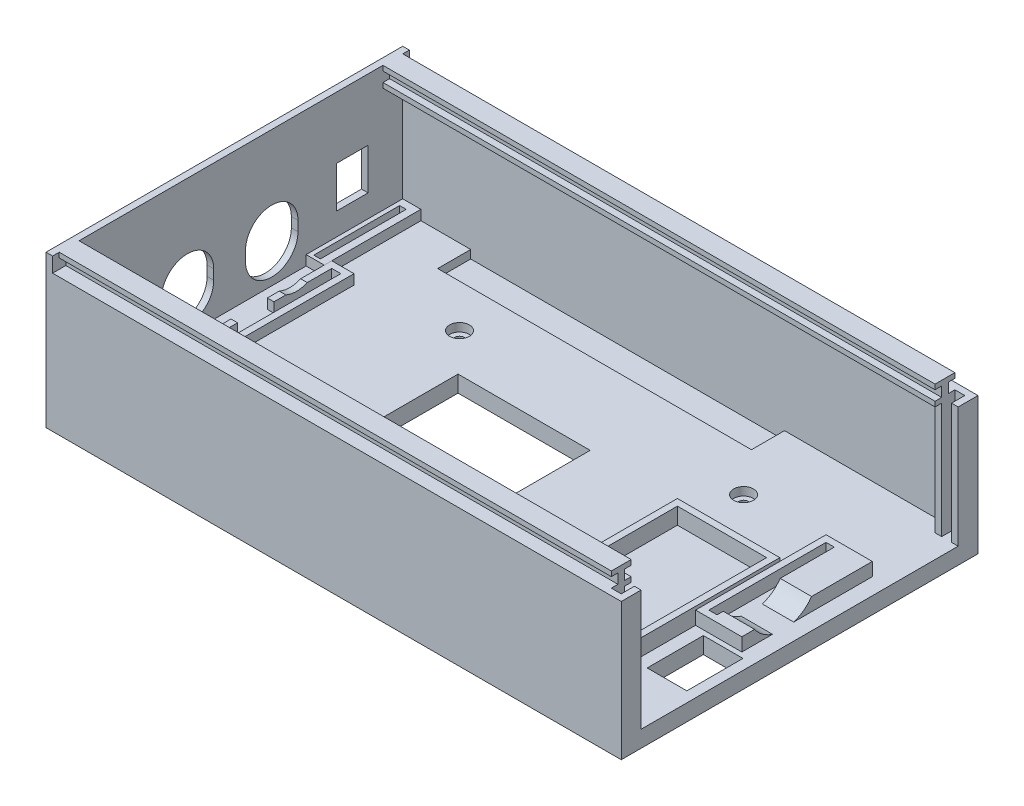
SolidWorks part; units mm, degrees
other "초음파센서_받침"
other "하단베이스"
other "모터헷_받침"
other "전자석_받침"
other "카메라_받침"
ref_plane "정면" through (0, 0, 0) normal (0, 0, 1) x (1, 0, 0)
ref_plane "윗면" through (0, 0, 0) normal (0, 1, 0) x (1, 0, 0)
ref_plane "우측면" through (0, 0, 0) normal (1, 0, 0) x (0, 0, -1)
sketch "스케치1" plane through (0, 0, 0) normal (0, 1, 0) x (1, 0, 0)
  line L1 (-87.075, 54) -> (87.075, 54)
  line L2 (-87.075, 54) -> (-87.075, -54)
  line L3 (-87.075, -54) -> (87.075, -54)
  line L4 (87.075, 54) -> (87.075, -54)
  line L5 (-87.075, 54) -> (87.075, -54) construction
  line L6 (-87.075, -54) -> (87.075, 54) construction
  point P0 (0, 0)
  dimension "D1" = 174.15
  dimension "D2" = 108
extrude "보스-돌출1" add sketch "스케치1" along normal blind 63
sketch "스케치2" plane through (87.075, 0, 0) normal (1, 0, 0) x (0, 0, -1)
  line L0 (-54, 0) -> (54, 0) construction
  line L1 (-52, 61) -> (52, 61)
  line L2 (-52, 61) -> (-52, 5)
  line L3 (-52, 5) -> (52, 5)
  line L4 (52, 61) -> (52, 5)
  line L5 (54, 63) -> (54, 0) construction
  line L6 (-54, 63) -> (-54, 0) construction
  line L7 (-54, 63) -> (54, 63) construction
  dimension "D1" = 5
  dimension "D2" = 2
  dimension "D3" = 2
  dimension "D4" = 2
extrude "컷-돌출1" cut sketch "스케치2" against normal blind 172.15
sketch "스케치3" plane through (0, 63, 0) normal (0, 1, 0) x (1, 0, 0)
  line L4 (87.075, -54) -> (87.075, 54)
  line L5 (87.075, 54) -> (-87.075, 54)
  line L6 (-87.075, 54) -> (-87.075, -54)
  line L7 (-87.075, -54) -> (87.075, -54)
  line L8 (87.075, -54) -> (87.075, 54)
  line L9 (87.075, 54) -> (-87.075, 54)
  line L10 (-87.075, 54) -> (-87.075, -54)
  line L11 (-87.075, -54) -> (87.075, -54)
  dimension "D1" = 0
extrude "컷-돌출2" cut sketch "스케치3" against normal blind 2
sketch "스케치4" plane through (0, 5, 0) normal (0, 1, 0) x (1, 0, 0)
  line L6 (-74.825, 23) -> (-74.825, -23)
  line L7 (-77.575, -23) -> (-74.825, -23)
  line L8 (-77.575, 23) -> (-77.575, -23)
  line L9 (-77.575, 23) -> (-74.825, 23)
  line L10 (-79.575, 25) -> (-72.825, 25)
  line L11 (-72.825, 25) -> (-72.825, -25)
  line L12 (-79.575, -25) -> (-72.825, -25)
  line L13 (-79.575, 25) -> (-79.575, -25)
  dimension "D6" = 2
sketch "스케치5" plane through (-87.075, 0, 0) normal (-1, 0, 0) x (0, 0, 1)
  line L0 (-12.34, 15.25) -> (-12.34, 18.25) construction
  line L1 (13.16, 15.25) -> (13.16, 18.25) construction
  line L2 (-20.28, 18.25) -> (-20.28, 15.25)
  line L3 (-4.4, 18.25) -> (-4.4, 15.25)
  line L4 (5.22, 18.25) -> (5.22, 15.25)
  line L5 (21.1, 18.25) -> (21.1, 15.25)
  arc A0 (-20.28, 15.25) -> (-4.4, 15.25) centre (-12.34, 15.25) ccw
  arc A1 (5.22, 15.25) -> (21.1, 15.25) centre (13.16, 15.25) ccw
  arc A2 (-4.4, 18.25) -> (-20.28, 18.25) centre (-12.34, 18.25) ccw
  arc A3 (21.1, 18.25) -> (5.22, 18.25) centre (13.16, 18.25) ccw
  dimension "D2" = 15.88
  dimension "D3" = 3
  dimension "D4" = 15.88
  dimension "D1" = 3
extrude "컷-돌출3" cut sketch "스케치5" against normal blind 10
extrude "보스-돌출2" add sketch "스케치4" along normal blind 3 separate body
sketch "스케치6" plane through (-79.575, 0, 0) normal (-1, 0, 0) x (0, 0, 1)
  circle A0 centre (-12.34, 15.25) radius 7.94
  circle A1 centre (13.16, 15.25) radius 7.94
extrude "컷-돌출4" cut sketch "스케치6" against normal blind 3
sketch "스케치7" plane through (-79.575, 0, 0) normal (-1, 0, 0) x (0, 0, 1)
  line L0 (-9.1025, 8) -> (9.9225, 8) construction
  line L1 (-5.5, 8) -> (5.5, 8)
  line L2 (-5.5, 8) -> (-5.5, 5)
  line L3 (-5.5, 5) -> (5.5, 5)
  line L4 (5.5, 8) -> (5.5, 5)
  line L5 (-25, 5) -> (25, 5) construction
  line L6 (-25, 8) -> (-25, 5) construction
  dimension "D1" = 11
  dimension "D2" = 19.5
extrude "컷-돌출5" cut sketch "스케치7" against normal blind 3
sketch "스케치8" plane through (87.075, 0, 0) normal (1, 0, 0) x (0, 0, -1)
  line L0 (0, 0) -> (0, 15) construction
  circle A0 centre (0, 15) radius 4
  dimension "D2" = 8
  dimension "D1" = 15
sketch "스케치13" plane through (0, 5, 0) normal (0, 1, 0) x (1, 0, 0)
  line L0 (70.075, 25) -> (70.075, -10.5)
  line L5 (70.075, -10.5) -> (72.575, -10.5)
  line L6 (72.575, 25) -> (72.575, -10.5)
  line L7 (70.075, 25) -> (72.575, 25)
  line L8 (68.075, 27) -> (68.075, -12.5)
  line L9 (68.075, -12.5) -> (74.575, -12.5)
  line L10 (74.575, 27) -> (74.575, -12.5)
  line L11 (68.075, 27) -> (74.575, 27)
  dimension "D2" = 2
extrude "보스-돌출5" add sketch "스케치13" along normal blind 4 separate body
sketch "스케치14" plane through (74.575, 0, 0) normal (1, 0, 0) x (0, 0, -1)
  line L4 (-12.5, 5) -> (27, 5)
  line L5 (27, 5) -> (27, 9)
  line L6 (27, 9) -> (-12.5, 9)
  line L7 (-12.5, 9) -> (-12.5, 5)
  line L8 (-12.5, 5) -> (27, 5)
  line L9 (27, 5) -> (27, 9)
  line L10 (27, 9) -> (-12.5, 9)
  line L11 (-12.5, 9) -> (-12.5, 5)
  dimension "D1" = 0
extrude "보스-돌출6" add sketch "스케치14" along normal up to surface (12.5 mm away) up to face at (87.075, 31.75, 0)
sketch "스케치15" plane through (87.075, 0, 0) normal (1, 0, 0) x (0, 0, -1)
  circle A0 centre (0, 15) radius 10.5
  line M1 (-12.5, 5) -> (27, 5)
  line M3 (27, 9) -> (-12.5, 9)
  dimension "D1" = 21
extrude "컷-돌출9" cut sketch "스케치15" against normal up to surface (14.5 mm away) contours A0 M3 M1 region at (87.075, 7.2591, 0) up to face at (72.575, 7, -7.25)
sketch "스케치16" plane through (0, 0, 0) normal (0, -1, 0) x (-1, 0, 0)
  line L0 (-71.925, -31) -> (-71.925, -14)
  line L5 (-71.925, -14) -> (-83.925, -14)
  line L6 (-83.925, -31) -> (-83.925, -14)
  line L7 (-71.925, -31) -> (-83.925, -31)
  circle A0 centre (44.9261, -28.968) radius 1.45
  circle A1 centre (44.9263, 29.0311) radius 1.45
  circle A2 centre (-41.0739, -28.9678) radius 1.45
  circle A3 centre (-41.0728, 29.0327) radius 1.45
  dimension "D1" = 2.9
  dimension "D2" = 2.9
  dimension "D3" = 2.9
  dimension "D4" = 2.9
extrude "컷-돌출10" cut sketch "스케치16" against normal up to surface (5 mm away) contours A0 | A1 | A3 | A2 | L7 L0 L5 L6 region at (77.925, 0, 22.5) region at (-44.9261, 0, 28.968) region at (-44.9263, 0, -29.0311) region at (41.0739, 0, 28.9678) region at (41.0728, 0, -29.0327) up to face at (1, 5, 0)
sketch "스케치17" plane through (0, 5, 0) normal (0, 1, 0) x (1, 0, 0)
  circle A0 centre (-44.9263, 29.0311) radius 3
  circle A1 centre (-44.9261, -28.968) radius 3
  circle A2 centre (41.0728, 29.0327) radius 3
  circle A3 centre (41.0739, -28.9678) radius 3
  dimension "D1" = 6
  dimension "D2" = 6
  dimension "D3" = 6
  dimension "D4" = 6
extrude "컷-돌출11" cut sketch "스케치17" against normal blind 2.5
sketch "스케치19" plane through (0, 5, 0) normal (0, 1, 0) x (1, 0, 0)
  line L0 (-85.075, -52) -> (87.075, -52) construction
  line L1 (40.075, 10) -> (65.075, 10)
  line L2 (40.075, 10) -> (40.075, -52)
  line L4 (65.075, 10) -> (65.075, -52)
  line L5 (66.075, 11) -> (66.075, -52)
  line L6 (39.075, 11) -> (66.075, 11)
  line L7 (39.075, 11) -> (39.075, -52)
  line L8 (65.075, -52) -> (66.075, -52)
  line L9 (40.075, -52) -> (39.075, -52)
  line L10 (68.075, 13) -> (68.075, -52)
  line L11 (37.075, 13) -> (68.075, 13)
  line L12 (37.075, 13) -> (37.075, -52)
  line L13 (66.075, -52) -> (68.075, -52)
  line L14 (39.075, -52) -> (37.075, -52)
  line L15 (68.075, 27) -> (68.075, -12.5) construction
  circle M9 centre (41.0739, -28.9678) radius 3
  line M14 (-85.075, -52) -> (87.075, -52)
  dimension "D3" = 31
  dimension "D4" = 27
  dimension "D5" = 25
  dimension "D6" = 2
  dimension "D1" = 1
  dimension "D2" = 2
extrude "보스-돌출7" add sketch "스케치19" along normal blind 5 separate body contours L11 L12 L7 L6 L5 L10 M14 M9 region at (37.3538, 5, 28.9678)
sketch "스케치20" plane through (37.075, 0, 0) normal (-1, 0, 0) x (0, 0, 1)
  line L0 (-13, 10) -> (52, 10) construction
  line L1 (16.1526, 10) -> (25.7505, 10)
  line L2 (16.1526, 10) -> (16.1526, 5)
  line L3 (16.1526, 5) -> (25.7505, 5)
  line L4 (25.7505, 10) -> (25.7505, 5)
  line L5 (-13, 5) -> (52, 5) construction
extrude "컷-돌출13" cut sketch "스케치20" against normal blind 5
ref_plane "평면1" through (0, 46, 0) normal (0, 1, 0) x (1, 0, 0)
sketch "스케치22" plane through (0, 46, 0) normal (0, 1, 0) x (1, 0, 0)
  line L1 (-87.075, 54) -> (87.075, 54)
  line L2 (-87.075, 54) -> (-87.075, -54)
  line L3 (-87.075, -54) -> (87.075, -54)
  line L4 (87.075, 54) -> (87.075, -54)
extrude "컷-돌출14" cut sketch "스케치22" along normal up to surface (15 mm away) up to face at (0.5, 61, 0)
sketch "스케치29" plane through (0, 0, 0) normal (0, -1, 0) x (-1, 0, 0)
  line L1 (33.7542, -22.5802) -> (-6.2458, -22.5802)
  line L2 (33.7542, -22.5802) -> (33.7542, 17.4198)
  line L3 (33.7542, 17.4198) -> (-6.2458, 17.4198)
  line L4 (-6.2458, -22.5802) -> (-6.2458, 17.4198)
  dimension "D1" = 40
  dimension "D2" = 40
extrude "컷-돌출21" cut sketch "스케치29" against normal up to surface (5 mm away) up to face at (-44.9261, 5, 31.968)
sketch "스케치30" plane through (0, 5, 0) normal (0, 1, 0) x (1, 0, 0)
  line L0 (-85.075, 52) -> (87.075, 52) construction
  line L1 (-64.5028, 52) -> (30.4972, 52)
  line L2 (-64.5028, 52) -> (-64.5028, 42)
  line L3 (-64.5028, 42) -> (30.4972, 42)
  line L4 (30.4972, 52) -> (30.4972, 42)
  line L5 (30.4972, -46) -> (30.4972, 52) construction
  dimension "D1" = 10
  dimension "D2" = 95
extrude "컷-돌출22" cut sketch "스케치30" against normal blind 2.5
sketch "스케치36" plane through (0, 46, 0) normal (0, 1, 0) x (1, 0, 0)
  line L16 (-85.075, 46) -> (87.075, 46)
  line L17 (87.075, -46) -> (-85.075, -46)
  line L18 (-85.075, 52) -> (-85.075, 46)
  line L19 (87.075, 52) -> (87.075, 46)
  line L20 (87.075, -52) -> (87.075, -46)
  line L21 (-85.075, -52) -> (-85.075, -46)
  line L24 (87.075, -52) -> (-85.075, -52)
  line L25 (-85.075, -52) -> (-85.075, 52)
  line L26 (-85.075, 52) -> (87.075, 52)
  line L27 (87.075, 52) -> (87.075, 54)
  line L28 (87.075, 54) -> (-87.075, 54)
  line L29 (-87.075, 54) -> (-87.075, -54)
  line L30 (-87.075, -54) -> (87.075, -54)
  line L31 (87.075, -54) -> (87.075, -52)
  line L32 (87.075, -52) -> (-85.075, -52)
  line L33 (-85.075, -52) -> (-85.075, 52)
  line L34 (-85.075, 52) -> (87.075, 52)
  line L35 (87.075, 52) -> (87.075, 54)
  line L36 (87.075, 54) -> (-87.075, 54)
  line L37 (-87.075, 54) -> (-87.075, -54)
  line L38 (-87.075, -54) -> (87.075, -54)
  line L39 (87.075, -54) -> (87.075, -52)
  line M9 (87.075, -52) -> (-85.075, -52)
  line M10 (-85.075, -52) -> (-85.075, 52)
  line M11 (-85.075, 52) -> (87.075, 52)
  dimension "D1" = 0
  dimension "D2" = 6
extrude "보스-돌출12" add sketch "스케치36" against normal blind 6 contours L19 L16 M11 M10 | L20 L17 M9 M10 region at (1, 46, -49) region at (1, 46, 49)
sketch "스케치37" plane through (87.075, 0, 0) normal (1, 0, 0) x (0, 0, -1)
  line L0 (-46, 40) -> (-46, 46) construction
  line L1 (-46, 44.5) -> (-48, 44.5)
  line L3 (-46, 41.5) -> (-48, 41.5)
  line L4 (-48, 44.5) -> (-48, 41.5)
  line L5 (-52, 40) -> (-46, 40) construction
  line L6 (-49, 40) -> (-49, 46) construction
  line L7 (-54, 46) -> (-46, 46) construction
  line L8 (-50, 44.5) -> (-50, 41.5)
  line L9 (-52, 41.5) -> (-50, 41.5)
  line L11 (-52, 44.5) -> (-50, 44.5)
  line L12 (-52, 44.5) -> (-52, 46)
  line L13 (-52, 46) -> (-54, 46)
  line L14 (-54, 46) -> (-54, 41.5)
  line L15 (-54, 46) -> (-54, 0) construction
  line L16 (-54, 41.5) -> (-52, 41.5)
  line L17 (-44, 41.5) -> (-46, 41.5)
  line L18 (-44, 46) -> (-44, 41.5)
  line L19 (-46, 46) -> (-44, 46)
  line L20 (-46, 44.5) -> (-46, 46)
  line L21 (0, 0) -> (0, 46) construction
  line L22 (46, 46) -> (-46, 46) construction
  line L23 (49, 40) -> (49, 46) construction
  line L24 (46, 44.5) -> (46, 46)
  line L25 (46, 46) -> (44, 46)
  line L26 (44, 46) -> (44, 41.5)
  line L27 (44, 41.5) -> (46, 41.5)
  line L28 (54, 41.5) -> (52, 41.5)
  line L29 (54, 46) -> (54, 41.5)
  line L30 (52, 46) -> (54, 46)
  line L31 (52, 44.5) -> (52, 46)
  line L32 (52, 44.5) -> (50, 44.5)
  line L33 (52, 41.5) -> (50, 41.5)
  line L34 (50, 44.5) -> (50, 41.5)
  line L35 (48, 44.5) -> (48, 41.5)
  line L36 (46, 41.5) -> (48, 41.5)
  line L37 (46, 44.5) -> (48, 44.5)
  dimension "D1" = 3
  dimension "D2" = 1.5
  dimension "D3" = 2
extrude "컷-돌출27" cut sketch "스케치37" against normal up to surface (174.15 mm away) up to face at (-87.075, 16.75, 13.16)
sketch "스케치38" plane through (-87.075, 0, 0) normal (-1, 0, 0) x (0, 0, 1)
  line L1 (-44, 41.5) -> (44, 41.5)
  line L2 (-44, 41.5) -> (-44, 46)
  line L3 (-44, 46) -> (44, 46)
  line L4 (44, 41.5) -> (44, 46)
extrude "컷-돌출28" cut sketch "스케치38" against normal blind 10
sketch "스케치41" plane through (0, 41.5, 0) normal (0, 1, 0) x (1, 0, 0)
  line L0 (-87.075, -54) -> (87.075, -54) construction
  line L1 (-87.075, 54) -> (-85.075, 54)
  line L2 (-87.075, 54) -> (-87.075, -54)
  line L3 (-87.075, -54) -> (-85.075, -54)
  line L4 (-85.075, 54) -> (-85.075, -54)
  dimension "D1" = 2
extrude "보스-돌출15" add sketch "스케치41" along normal up to surface (4.5 mm away) up to face at (0, 46, 49)
sketch "스케치42" plane through (0, 46, 0) normal (0, 1, 0) x (1, 0, 0)
  line L0 (-85.075, 54) -> (87.075, 54) construction
  line L1 (82.075, 52) -> (85.075, 52)
  line L2 (82.075, 52) -> (82.075, -52)
  line L3 (82.075, -52) -> (85.075, -52)
  line L4 (85.075, 52) -> (85.075, -52)
  line L5 (-85.075, -54) -> (87.075, -54) construction
  line L6 (87.075, -52) -> (87.075, 52) construction
  line L7 (87.075, 46) -> (87.075, 52) construction
  line L8 (87.075, 48) -> (85.075, 48)
  line L9 (87.075, 48) -> (87.075, -48)
  line L10 (87.075, -48) -> (85.075, -48)
  line L11 (85.075, 48) -> (85.075, -48)
  point P6 (83.575, -52)
  line M4 (-85.075, -52) -> (87.075, -52)
  line M5 (87.075, -52) -> (87.075, -46)
  line M6 (87.075, -46) -> (-85.075, -46)
  line M8 (-85.075, 46) -> (87.075, 46)
  line M9 (87.075, 46) -> (87.075, 52)
  line M10 (87.075, 52) -> (-85.075, 52)
  dimension "D1" = 3
  dimension "D2" = 2
  dimension "D3" = 2
  dimension "D4" = 2
  dimension "D5" = 6
  dimension "D6" = 6
extrude "컷-돌출29" cut sketch "스케치42" against normal up to surface (41 mm away) contours L4 L2 M8 M6 | L9 L4 M8 M6 | L4 L2 M6 M4 | L4 L2 M10 M8 | L8 L4 M9 M8 | L10 L4 M5 M6 region at (83.575, 46, -49) region at (83.575, 46, 0) region at (86.075, 46, -47) region at (83.575, 46, 49) region at (86.075, 46, 0) region at (86.075, 46, 47) up to face at (-13.7542, 5, 2.5802)
sketch "스케치43" plane through (0, 0, -52) normal (0, 0, 1) x (1, 0, 0)
  line L1 (87.075, 5) -> (85.075, 5)
  line L2 (87.075, 5) -> (87.075, 40)
  line L3 (87.075, 40) -> (85.075, 40)
  line L4 (85.075, 5) -> (85.075, 40)
extrude "보스-돌출17" add sketch "스케치43" along normal blind 4
sketch "스케치44" plane through (0, 0, 52) normal (0, 0, -1) x (-1, 0, 0)
  line L1 (-87.075, 5) -> (-85.075, 5)
  line L2 (-87.075, 5) -> (-87.075, 40)
  line L3 (-87.075, 40) -> (-85.075, 40)
  line L4 (-85.075, 5) -> (-85.075, 40)
extrude "보스-돌출18" add sketch "스케치44" along normal blind 4
sketch "스케치48" plane through (-87.075, 0, 0) normal (-1, 0, 0) x (0, 0, 1)
  line L0 (-41.5075, 27.3) -> (-32.0075, 27.3)
  line L5 (-32.0075, 27.3) -> (-32.0075, 14.8)
  line L6 (-41.5075, 14.8) -> (-32.0075, 14.8)
  line L7 (-41.5075, 27.3) -> (-41.5075, 14.8)
  dimension "D1" = 12.5
extrude "컷-돌출30" cut sketch "스케치48" against normal blind 10
sketch "스케치49" plane through (0, 5, 0) normal (0, 1, 0) x (1, 0, 0)
  line L0 (-81.775, 49.7575) -> (-81.775, 23.7575)
  line L1 (-83.275, 49.2575) -> (-82.275, 49.2575)
  line L2 (-83.275, 49.2575) -> (-83.275, 24.2575)
  line L3 (-83.275, 24.2575) -> (-82.275, 24.2575)
  line L4 (-82.275, 49.2575) -> (-82.275, 24.2575)
  line L5 (-83.775, 23.7575) -> (-81.775, 23.7575)
  line L6 (-83.775, 49.7575) -> (-83.775, 23.7575)
  line L7 (-83.775, 49.7575) -> (-81.775, 49.7575)
  line L8 (-79.575, 51.9975) -> (-79.575, 22.7408)
  line L9 (-85.075, 22.7408) -> (-79.575, 22.7408)
  line L11 (-85.075, 51.9975) -> (-79.575, 51.9975)
  line L14 (-85.075, 52) -> (-85.075, 22.7408)
  line L15 (-85.075, -52) -> (-85.075, 52) construction
  line M29 (-85.075, 52) -> (-85.075, -52)
  dimension "D2" = 2.24
  dimension "D3" = 2.2
  dimension "D1" = 0.5
extrude "보스-돌출19" add sketch "스케치49" along normal blind 3 separate body contours L11 L9 L8 L6 L7 L0 L5 M29 region at (-79.8727, 5, -37.3692)
sketch "스케치51" plane through (0, 46, 0) normal (0, 1, 0) x (1, 0, 0)
  line L1 (85.075, 52) -> (87.075, 52)
  line L2 (85.075, 52) -> (85.075, -52)
  line L3 (85.075, -52) -> (87.075, -52)
  line L4 (87.075, 52) -> (87.075, -52)
extrude "컷-돌출31" cut sketch "스케치51" against normal up to surface (4.5 mm away) up to face at (42.2875, 41.5, 51.5)
sketch "스케치52" plane through (0, 0, -52) normal (0, 0, 1) x (1, 0, 0)
  line L0 (30.4972, 5) -> (85.075, 5) construction
  line L1 (82.075, 40) -> (80.075, 40)
  line L2 (82.075, 40) -> (82.075, 5)
  line L3 (82.075, 5) -> (80.075, 5)
  line L4 (80.075, 40) -> (80.075, 5)
  dimension "D1" = 2
extrude "보스-돌출20" add sketch "스케치52" along normal blind 4
sketch "스케치53" plane through (0, 0, 52) normal (0, 0, -1) x (-1, 0, 0)
  line L0 (85.075, 5) -> (-85.075, 5) construction
  line L1 (-82.075, 40) -> (-80.075, 40)
  line L2 (-82.075, 40) -> (-82.075, 5)
  line L3 (-82.075, 5) -> (-80.075, 5)
  line L4 (-80.075, 40) -> (-80.075, 5)
  dimension "D1" = 2
extrude "보스-돌출21" add sketch "스케치53" along normal blind 4
sketch "스케치55" plane through (0, 5, 0) normal (0, 1, 0) x (1, 0, 0)
  line L0 (86.825, -47.5) -> (86.825, 47.5)
  line L1 (86.825, 47.5) -> (84.825, 47.5)
  line L2 (84.825, 47.5) -> (84.825, 51.5)
  line L3 (84.825, 51.5) -> (82.325, 51.5)
  line L4 (82.325, 51.5) -> (82.325, -51.5)
  line L5 (82.325, -51.5) -> (84.825, -51.5)
  line L6 (84.825, -51.5) -> (84.825, -47.5)
  line L7 (84.825, -47.5) -> (86.825, -47.5)
  line L8 (82.075, 52) -> (85.075, 52) construction
  line L9 (82.075, 52) -> (82.075, 46) construction
  line L10 (85.075, 48) -> (85.075, 52) construction
  dimension "D1" = 103
  dimension "D2" = 0.5
  dimension "D3" = 0.25
  dimension "D4" = 0.25
